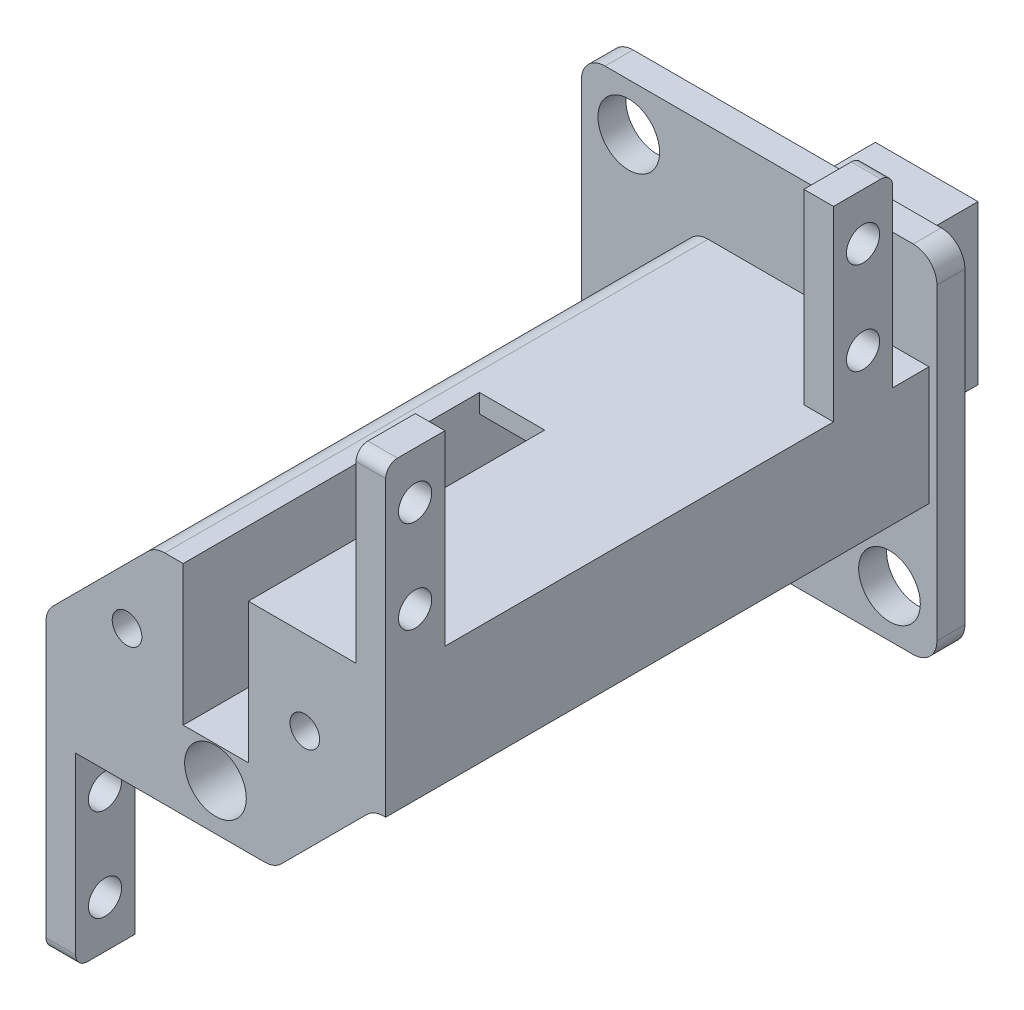
SolidWorks part; units mm, degrees
ref_plane "Front Plane" through (0, 0, 0) normal (0, 0, 1) x (1, 0, 0)
ref_plane "Top Plane" through (0, 0, 0) normal (0, 1, 0) x (1, 0, 0)
ref_plane "Right Plane" through (0, 0, 0) normal (1, 0, 0) x (0, 0, -1)
sketch "Sketch1" plane through (0, 0, 0) normal (0, 0, 1) x (1, 0, 0)
  line L1 (0, 0) -> (7, 0)
  line L2 (0, 0) -> (0, 13)
  line L3 (0, 13) -> (7, 13)
  line L4 (7, 0) -> (7, 13)
  line L5 (-2, -2) -> (9, -2)
  line L6 (-2, -2) -> (-2, 15)
  line L7 (-2, 15) -> (9, 15)
  line L8 (9, -2) -> (9, 15)
  dimension "D1" = 7
  dimension "D2" = 13
  dimension "D3" = 2
  dimension "D4" = 2
  dimension "D5" = 2
  dimension "D6" = 2
extrude "Boss-Extrude1" add sketch "Sketch1" along normal blind 76.2
sketch "Sketch2" plane through (0, 0, 0) normal (0, 0, -1) x (-1, 0, 0)
  line L1 (-9, -2) -> (2, -2)
  line L2 (-9, -2) -> (-9, 15)
  line L3 (-9, 15) -> (2, 15)
  line L4 (2, -2) -> (2, 15)
extrude "Boss-Extrude2" add sketch "Sketch2" along normal blind 2
sketch "Sketch3" plane through (0, -2, 0) normal (0, -1, 0) x (-1, 0, 0)
  line L0 (-9, 2) -> (2, 2) construction
  line L1 (-7, 0) -> (0, 0)
  line L2 (-7, 0) -> (-7, -11)
  line L3 (-7, -11) -> (0, -11)
  line L4 (0, 0) -> (0, -11)
  line L5 (2, -76.2) -> (2, 2) construction
  line L6 (-9, -76.2) -> (-9, 2) construction
  dimension "D1" = 2
  dimension "D2" = 2
  dimension "D3" = 2
  dimension "D4" = 11
extrude "Cut-Extrude1" cut sketch "Sketch3" against normal up to surface (2 mm away) up to face at (3.5, 0, 38.1)
ref_plane "Plane1" through (0, 0, 14.986) normal (0, 0, 1) x (1, 0, 0)
sketch "Sketch4" plane through (0, 0, 14.986) normal (0, 0, 1) x (1, 0, 0)
  line L2 (-2, 15) -> (9, 15)
  line L3 (-2, 15) -> (-2, -2)
  line L4 (-2, -2) -> (9, -2)
  line L5 (9, 15) -> (9, -2)
  line L6 (-15.55, 25.55) -> (22.55, 25.55)
  line L7 (-15.55, 25.55) -> (-15.55, -12.55)
  line L8 (-15.55, -12.55) -> (22.55, -12.55)
  line L9 (22.55, 25.55) -> (22.55, -12.55)
  dimension "D4" = 38.1
  dimension "D5" = 38.1
extrude "Boss-Extrude3" add sketch "Sketch4" along normal blind 3
sketch "Sketch5" plane through (0, 0, 14.986) normal (0, 0, -1) x (-1, 0, 0)
  line L0 (-22.55, 25.55) -> (15.55, 25.55) construction
  line L1 (-9, 15) -> (2, 15)
  line L2 (-9, 15) -> (-9, -2)
  line L3 (-9, -2) -> (2, -2)
  line L4 (2, 15) -> (2, -2)
  line L5 (15.55, 25.55) -> (15.55, -12.55) construction
  circle A0 centre (-3.5, 6.5) radius 12.7
  dimension "D1" = 25.4
  dimension "D2" = 19.05
  dimension "D3" = 19.05
  dimension "D4" = 10.55
  dimension "D5" = 13.55
  dimension "D6" = 17
  dimension "D7" = 11
extrude "Boss-Extrude4" add sketch "Sketch5" along normal blind 2.54
sketch "Sketch6" plane through (0, -2, 0) normal (0, -1, 0) x (1, 0, 0)
  line L1 (9, 76.2) -> (-2, 76.2)
  line L2 (9, 76.2) -> (9, 17.986)
  line L3 (9, 17.986) -> (-2, 17.986)
  line L4 (-2, 76.2) -> (-2, 17.986)
extrude "Boss-Extrude5" add sketch "Sketch6" along normal blind 6.35
sketch "Sketch7" plane through (0, 0, 76.2) normal (0, 0, 1) x (1, 0, 0)
  line L0 (-2, 15) -> (-2, -8.35) construction
  line L1 (0, 0) -> (7, 0) construction
  circle A0 centre (3.461, -3.429) radius 3.302
  dimension "D3" = 6.604
  dimension "D1" = 5.461
  dimension "D2" = 3.429
extrude "Cut-Extrude2" cut sketch "Sketch7" against normal up to surface (78.2 mm away) up to face at (3.5, 6.5, -2)
sketch "Sketch8" plane through (0, 15, 0) normal (0, 1, 0) x (1, 0, 0)
  line L0 (9, -76.2) -> (-2, -76.2) construction
  line L1 (0, -76.2) -> (6.985, -76.2)
  line L2 (0, -76.2) -> (0, -44.45)
  line L3 (0, -44.45) -> (6.985, -44.45)
  line L4 (6.985, -76.2) -> (6.985, -44.45)
  dimension "D1" = 6.985
  dimension "D2" = 31.75
extrude "Cut-Extrude3" cut sketch "Sketch8" against normal blind 6.35
sketch "Sketch9" plane through (9, 0, 0) normal (1, 0, 0) x (0, 0, -1)
  line L1 (-76.2, 15) -> (-17.78, 15)
  line L2 (-76.2, 15) -> (-76.2, 2.3)
  line L3 (-76.2, 2.3) -> (-17.78, 2.3)
  line L4 (-17.78, 15) -> (-17.78, 2.3)
  dimension "D1" = 12.7
  dimension "D2" = 58.42
extrude "Boss-Extrude6" add sketch "Sketch9" along normal blind 12.7
sketch "Sketch10" plane through (0, 15, 0) normal (0, 1, 0) x (1, 0, 0)
  line L0 (20.5485, -17.986) -> (-2, -17.986) construction
  line L1 (21.7, -76.2) -> (18.525, -76.2)
  line L2 (21.7, -76.2) -> (21.7, -17.986)
  line L3 (21.7, -17.986) -> (18.525, -17.986)
  line L4 (18.525, -76.2) -> (18.525, -17.986)
  dimension "D1" = 3.175
extrude "Boss-Extrude7" add sketch "Sketch10" along normal blind 20
sketch "Sketch11" plane through (18.525, 0, 0) normal (-1, 0, 0) x (0, 0, 1)
  line L1 (76.2, 15) -> (17.986, 15) construction
  line L2 (17.986, 35) -> (21.8701, 35)
  line L3 (17.986, 35) -> (17.986, 15)
  line L4 (17.986, 15) -> (21.8701, 15)
  line L5 (21.8701, 35) -> (21.8701, 15)
  circle A0 centre (25.05, 29.95) radius 1.778
  circle A1 centre (25.05, 20.05) radius 1.778
  circle A2 centre (73.05, 29.95) radius 1.778
  circle A3 centre (73.05, 20.05) radius 1.778
  dimension "D1" = 3.556
  dimension "D2" = 3.556
  dimension "D3" = 3.556
  dimension "D4" = 3.556
extrude "Cut-Extrude4" cut sketch "Sketch11" against normal through all
fillet "Fillet1" radius 1.27 2 edges at (20.1125, 35, 76.2) (20.1125, 35, 21.8701)
chamfer "Chamfer1" distance 11.43 angle 45 1 edges at (9, 2.3, 47.093)
fillet "Fillet3" radius 2.54 2 edges at (20.43, 2.3, 47.093) (9.78, -8.35, 47.093)
sketch "Sketch12" plane through (-2, 0, 0) normal (-1, 0, 0) x (0, 0, 1)
  line L0 (17.986, 15) -> (17.986, -8.35) construction
  line L1 (76.2, -8.35) -> (17.986, -8.35)
  line L2 (76.2, -8.35) -> (76.2, 3.325)
  line L3 (76.2, 3.325) -> (17.986, 3.325)
  line L4 (17.986, -8.35) -> (17.986, 3.325)
extrude "Boss-Extrude8" add sketch "Sketch12" along normal blind 12.7
sketch "Sketch13" plane through (0, -8.35, 0) normal (0, -1, 0) x (1, 0, 0)
  line L1 (-14.7, 76.2) -> (-11.525, 76.2)
  line L2 (-14.7, 76.2) -> (-14.7, 21.844)
  line L3 (-14.7, 21.844) -> (-11.525, 21.844)
  line L4 (-11.525, 76.2) -> (-11.525, 21.844)
  dimension "D1" = 54.356
  dimension "D2" = 3.175
extrude "Boss-Extrude9" add sketch "Sketch13" along normal blind 20
chamfer "Chamfer3" distance 12.7 angle 45 1 edges at (-2, 3.325, 47.093)
fillet "Fillet4" radius 2.54 2 edges at (-14.7, 3.325, 47.093) (-3.025, 15, 47.093)
sketch "Sketch14" plane through (0, -8.35, 0) normal (0, -1, 0) x (1, 0, 0)
  line L0 (8.7279, 17.986) -> (8.7279, 76.2) construction
  line L1 (6.6959, 70.194) -> (0.5999, 70.194)
  line L2 (6.6959, 70.194) -> (6.6959, 41.5999)
  line L3 (6.6959, 41.5999) -> (0.5999, 41.5999)
  line L4 (0.5999, 70.194) -> (0.5999, 41.5999)
  point P4 (6.6959, 55.8969)
  dimension "D1" = 2.032
  dimension "D2" = 6.096
extrude "Cut-Extrude5" cut sketch "Sketch14" against normal blind 6.35
sketch "Sketch15" plane through (-11.525, 0, 0) normal (1, 0, 0) x (0, 0, -1)
  circle A0 centre (-73.05, -13.4) radius 1.778
  circle A1 centre (-73.05, -23.3) radius 1.778
  circle A2 centre (-25.05, -13.4) radius 1.778
  circle A4 centre (-25.05, -23.3) radius 1.778
  dimension "D1" = 3.556
  dimension "D2" = 3.556
  dimension "D3" = 3.556
  dimension "D4" = 3.556
extrude "Cut-Extrude6" cut sketch "Sketch15" against normal through all
fillet "Fillet5" radius 1.27 2 edges at (-13.1125, -28.35, 21.844) (-13.1125, -28.35, 76.2)
sketch "Sketch16" plane through (0, 0, 76.2) normal (0, 0, 1) x (1, 0, 0)
  circle A0 centre (-6.0166, 5.9715) radius 1.5875
  circle A1 centre (13.0334, 5.9715) radius 1.5875
  dimension "D1" = 3.175
  dimension "D2" = 3.175
extrude "Cut-Extrude7" cut sketch "Sketch16" against normal blind 12.7
fillet "Fillet6" radius 2.54 4 edges at (-15.55, -12.55, 16.486) (22.55, -12.55, 16.486) (22.55, 25.55, 16.486) (-15.55, 25.55, 16.486)
sketch "Sketch17" plane through (0, 0, 17.986) normal (0, 0, 1) x (1, 0, 0)
  line L0 (22.55, -10.01) -> (22.55, 23.01) construction
  line L1 (-13.01, -12.55) -> (20.01, -12.55) construction
  line L2 (20.01, 25.55) -> (-13.01, 25.55) construction
  line L3 (-15.55, 23.01) -> (-15.55, -10.01) construction
  circle A0 centre (-10.47, 20.47) radius 3.302
  circle A1 centre (17.47, -7.47) radius 3.302
  dimension "D1" = 6.604
  dimension "D2" = 6.604
  dimension "D3" = 5.08
  dimension "D5" = 5.08
  dimension "D4" = 5.08
  dimension "D6" = 5.08
extrude "Cut-Extrude8" cut sketch "Sketch17" against normal through all
sketch "Sketch19" plane through (0, 0, -2) normal (0, 0, -1) x (-1, 0, 0)
  line L0 (2, -2) -> (2, 15) construction
  line L1 (-9, 15) -> (2, 15)
  line L2 (-9, 15) -> (-9, -2)
  line L3 (-9, -2) -> (2, -2)
  line L4 (2, 15) -> (2, -2)
extrude "Cut-Extrude9" cut sketch "Sketch19" against normal blind 2.032
ref_plane "Plane2" through (21.7, 35, 74.93) normal (0, 0, -1) x (-1, 0, 0)
sketch "Sketch21" plane through (21.7, 0, 0) normal (1, 0, 0) x (0, 0, -1)
  line L0 (-74.93, 35) -> (-23.1401, 35) construction
  line L1 (-69.85, 35) -> (-28.2201, 35)
  line L2 (-69.85, 35) -> (-69.85, 15)
  line L3 (-69.85, 15) -> (-28.2201, 15)
  line L4 (-28.2201, 35) -> (-28.2201, 15)
  line L5 (-76.2, 33.73) -> (-76.2, 2.3) construction
  line L6 (-21.8701, 33.73) -> (-21.8701, 15) construction
  dimension "D1" = 6.35
  dimension "D2" = 6.35
  dimension "D3" = 20
extrude "Cut-Extrude10" cut sketch "Sketch21" against normal blind 25.4
sketch "Sketch22" plane through (-14.7, 0, 0) normal (-1, 0, 0) x (0, 0, 1)
  line L0 (74.93, -28.35) -> (23.114, -28.35) construction
  line L1 (28.194, -28.35) -> (69.85, -28.35)
  line L2 (28.194, -28.35) -> (28.194, -8.35)
  line L3 (28.194, -8.35) -> (69.85, -8.35)
  line L4 (69.85, -28.35) -> (69.85, -8.35)
  line L5 (21.844, -27.08) -> (21.844, -8.35) construction
  line L6 (76.2, -27.08) -> (76.2, 2.2729) construction
  dimension "D1" = 6.35
  dimension "D2" = 20
  dimension "D3" = 6.35
extrude "Cut-Extrude11" cut sketch "Sketch22" against normal blind 25.4
equation "\"D3@Sketch15\"=\"D4@Sketch15\""
equation "\"D2@Sketch15\"=\"D4@Sketch15\""
equation "\"D1@Sketch15\"=\"D4@Sketch15\""
equation "\"D4@Sketch11\"=\"D3@Sketch11\""
equation "\"D1@Sketch11\"=\"D3@Sketch11\""
equation "\"D2@Sketch11\"=\"D3@Sketch11\""
